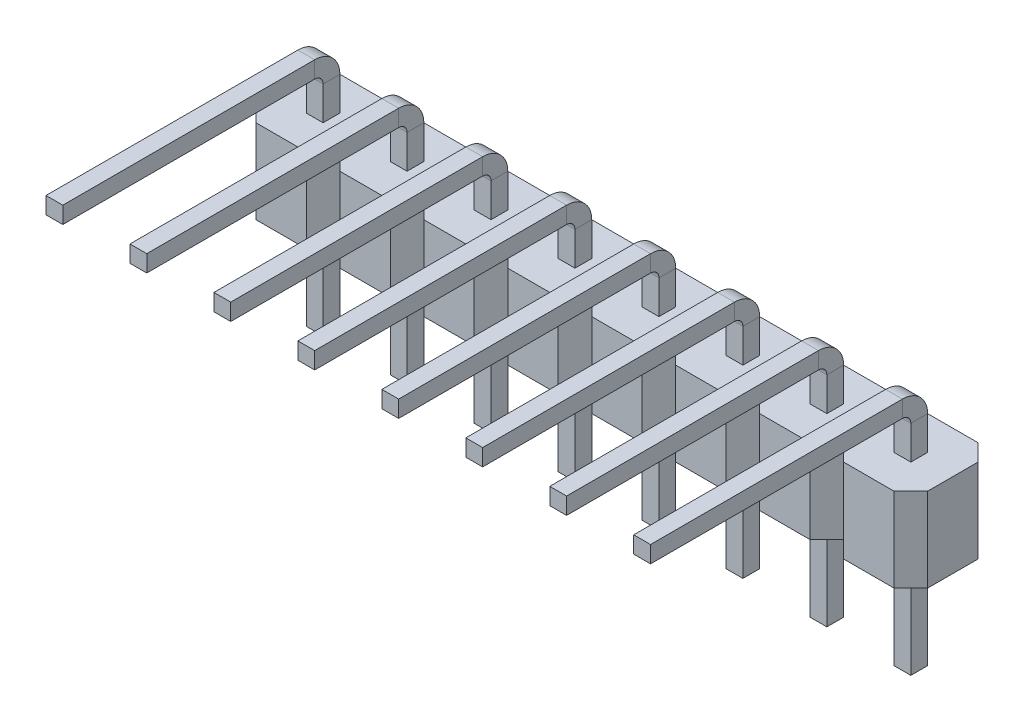
SolidWorks part; units mm, degrees
ref_plane "Front Plane" through (0, 0, 0) normal (0, 0, 1) x (1, 0, 0)
ref_plane "Top Plane" through (0, 0, 0) normal (0, 1, 0) x (1, 0, 0)
ref_plane "Right Plane" through (0, 0, 0) normal (1, 0, 0) x (0, 0, -1)
sketch "Sketch1" plane through (0, 0, 0) normal (0, 1, 0) x (1, 0, 0)
  line L0 (-1.25, 0.75) -> (-0.75, 1.25)
  line L1 (-0.75, -1.25) -> (0.75, -1.25)
  line L2 (-1.25, -0.75) -> (-1.25, 0.75)
  line L3 (-0.75, 1.25) -> (0.75, 1.25)
  line L5 (-1.25, -1.25) -> (1.25, 1.25) construction
  line L6 (-1.25, 1.25) -> (1.25, -1.25) construction
  line L7 (0.75, 1.25) -> (1.25, 0.75)
  line L8 (0.75, -1.25) -> (1.25, -0.75)
  line L9 (-1.25, -0.75) -> (-0.75, -1.25)
  line L11 (1.75, 1.25) -> (3.25, 1.25)
  line L12 (3.25, 1.25) -> (3.75, 0.75)
  line L13 (1.25, 0.75) -> (1.75, 1.25)
  line L15 (1.25, -0.75) -> (1.75, -1.25)
  line L16 (1.75, -1.25) -> (3.25, -1.25)
  line L17 (3.25, -1.25) -> (3.75, -0.75)
  line L18 (1.25, 1.25) -> (3.75, -1.25) construction
  line L19 (1.25, -1.25) -> (3.75, 1.25) construction
  line L21 (4.25, 1.25) -> (5.75, 1.25)
  line L22 (5.75, 1.25) -> (6.25, 0.75)
  line L23 (3.75, 0.75) -> (4.25, 1.25)
  line L25 (3.75, -0.75) -> (4.25, -1.25)
  line L26 (4.25, -1.25) -> (5.75, -1.25)
  line L27 (5.75, -1.25) -> (6.25, -0.75)
  line L28 (3.75, 1.25) -> (6.25, -1.25) construction
  line L29 (3.75, -1.25) -> (6.25, 1.25) construction
  line L31 (6.75, 1.25) -> (8.25, 1.25)
  line L32 (8.25, 1.25) -> (8.75, 0.75)
  line L33 (6.25, 0.75) -> (6.75, 1.25)
  line L35 (6.25, -0.75) -> (6.75, -1.25)
  line L36 (6.75, -1.25) -> (8.25, -1.25)
  line L37 (8.25, -1.25) -> (8.75, -0.75)
  line L38 (6.25, 1.25) -> (8.75, -1.25) construction
  line L39 (6.25, -1.25) -> (8.75, 1.25) construction
  line L41 (9.25, 1.25) -> (10.75, 1.25)
  line L42 (10.75, 1.25) -> (11.25, 0.75)
  line L43 (8.75, 0.75) -> (9.25, 1.25)
  line L45 (8.75, -0.75) -> (9.25, -1.25)
  line L46 (9.25, -1.25) -> (10.75, -1.25)
  line L47 (10.75, -1.25) -> (11.25, -0.75)
  line L48 (8.75, 1.25) -> (11.25, -1.25) construction
  line L49 (8.75, -1.25) -> (11.25, 1.25) construction
  line L51 (11.75, 1.25) -> (13.25, 1.25)
  line L52 (13.25, 1.25) -> (13.75, 0.75)
  line L53 (11.25, 0.75) -> (11.75, 1.25)
  line L55 (11.25, -0.75) -> (11.75, -1.25)
  line L56 (11.75, -1.25) -> (13.25, -1.25)
  line L57 (13.25, -1.25) -> (13.75, -0.75)
  line L58 (11.25, 1.25) -> (13.75, -1.25) construction
  line L59 (11.25, -1.25) -> (13.75, 1.25) construction
  line L61 (14.25, 1.25) -> (15.75, 1.25)
  line L62 (15.75, 1.25) -> (16.25, 0.75)
  line L63 (13.75, 0.75) -> (14.25, 1.25)
  line L65 (13.75, -0.75) -> (14.25, -1.25)
  line L66 (14.25, -1.25) -> (15.75, -1.25)
  line L67 (15.75, -1.25) -> (16.25, -0.75)
  line L68 (13.75, 1.25) -> (16.25, -1.25) construction
  line L69 (13.75, -1.25) -> (16.25, 1.25) construction
  line L70 (18.75, -0.75) -> (18.75, 0.75)
  line L71 (16.75, 1.25) -> (18.25, 1.25)
  line L72 (18.25, 1.25) -> (18.75, 0.75)
  line L73 (16.25, 0.75) -> (16.75, 1.25)
  line L75 (16.25, -0.75) -> (16.75, -1.25)
  line L76 (16.75, -1.25) -> (18.25, -1.25)
  line L77 (18.25, -1.25) -> (18.75, -0.75)
  line L78 (16.25, 1.25) -> (18.75, -1.25) construction
  line L79 (16.25, -1.25) -> (18.75, 1.25) construction
  line L80 (1.25, -0.75) -> (1.25, 0.75) [skipped]
  line L81 (3.75, -0.75) -> (3.75, 0.75) [skipped]
  line L82 (6.25, -0.75) -> (6.25, -0.032) [skipped]
  line L83 (8.75, -0.75) -> (8.75, 0.75) [skipped]
  line L84 (11.25, -0.75) -> (11.25, 0.75) [skipped]
  line L85 (13.75, -0.75) -> (13.75, 0.75) [skipped]
  line L86 (16.25, -0.75) -> (16.25, 0.75) [skipped]
  point P0 (0, 0)
  dimension "D1" = 2.5
  dimension "D2" = 2.5
  dimension "D3" = 8
extrude "Boss-Extrude1" add sketch "Sketch1" along normal blind 2.5
sketch "Sketch3" plane through (0, 0, 0) normal (1, 0, 0) x (0, 0, -1)
  line L0 (0, 2.5) -> (0, 3.5)
  line L1 (-0.75, 2.5) -> (0.75, 2.5) construction
  line L2 (-0.5, 4) -> (-8, 4)
  arc A0 (0, 3.5) -> (-0.5, 4) centre (-0.5, 3.5) ccw
  dimension "D2" = 0.5
  dimension "D1" = 1.5
  dimension "D3" = 8
sketch "Sketch2" plane through (0, 2.5, 0) normal (0, 1, 0) x (1, 0, 0)
  line L0 (2.25, 0.25) -> (2.75, 0.25)
  line L1 (-0.25, -0.25) -> (0.25, -0.25)
  line L2 (-0.25, -0.25) -> (-0.25, 0.25)
  line L3 (-0.25, 0.25) -> (0.25, 0.25)
  line L4 (0.25, -0.25) -> (0.25, 0.25)
  line L5 (-0.25, -0.25) -> (0.25, 0.25) construction
  line L6 (-0.25, 0.25) -> (0.25, -0.25) construction
  line L7 (2.75, -0.25) -> (2.75, 0.25)
  line L8 (2.25, 0.25) -> (2.75, -0.25) construction
  line L9 (2.25, -0.25) -> (2.75, -0.25)
  line L10 (2.25, -0.25) -> (2.75, 0.25) construction
  line L11 (2.25, -0.25) -> (2.25, 0.25)
  line L12 (4.75, 0.25) -> (5.25, 0.25)
  line L13 (5.25, -0.25) -> (5.25, 0.25)
  line L14 (4.75, 0.25) -> (5.25, -0.25) construction
  line L15 (4.75, -0.25) -> (5.25, -0.25)
  line L16 (4.75, -0.25) -> (5.25, 0.25) construction
  line L17 (4.75, -0.25) -> (4.75, 0.25)
  line L18 (7.25, 0.25) -> (7.75, 0.25)
  line L19 (7.75, -0.25) -> (7.75, 0.25)
  line L20 (7.25, 0.25) -> (7.75, -0.25) construction
  line L21 (7.25, -0.25) -> (7.75, -0.25)
  line L22 (7.25, -0.25) -> (7.75, 0.25) construction
  line L23 (7.25, -0.25) -> (7.25, 0.25)
  line L24 (9.75, 0.25) -> (10.25, 0.25)
  line L25 (10.25, -0.25) -> (10.25, 0.25)
  line L26 (9.75, 0.25) -> (10.25, -0.25) construction
  line L27 (9.75, -0.25) -> (10.25, -0.25)
  line L28 (9.75, -0.25) -> (10.25, 0.25) construction
  line L29 (9.75, -0.25) -> (9.75, 0.25)
  line L30 (12.25, 0.25) -> (12.75, 0.25)
  line L31 (12.75, -0.25) -> (12.75, 0.25)
  line L32 (12.25, 0.25) -> (12.75, -0.25) construction
  line L33 (12.25, -0.25) -> (12.75, -0.25)
  line L34 (12.25, -0.25) -> (12.75, 0.25) construction
  line L35 (12.25, -0.25) -> (12.25, 0.25)
  line L36 (14.75, 0.25) -> (15.25, 0.25)
  line L37 (15.25, -0.25) -> (15.25, 0.25)
  line L38 (14.75, 0.25) -> (15.25, -0.25) construction
  line L39 (14.75, -0.25) -> (15.25, -0.25)
  line L40 (14.75, -0.25) -> (15.25, 0.25) construction
  line L41 (14.75, -0.25) -> (14.75, 0.25)
  line L42 (17.25, 0.25) -> (17.75, 0.25)
  line L43 (17.75, -0.25) -> (17.75, 0.25)
  line L44 (17.25, 0.25) -> (17.75, -0.25) construction
  line L45 (17.25, -0.25) -> (17.75, -0.25)
  line L46 (17.25, -0.25) -> (17.75, 0.25) construction
  line L47 (17.25, -0.25) -> (17.25, 0.25)
  point P0 (0, 0)
  point P5 (2.5, 0)
  dimension "D1" = 0.5
  dimension "D2" = 0.5
  dimension "D4" = 2.5
  dimension "D3" = 8
extrude "Boss-Extrude3" add sketch "Sketch2" against normal blind 5.5
sweep "Sweep1" add profiles "Sketch2<3>" path "Sketch3"
sketch "Sketch2<3>" plane through (0, 2.5, 0) normal (0, 1, 0) x (1, 0, 0) same geometry as "Sketch2"
